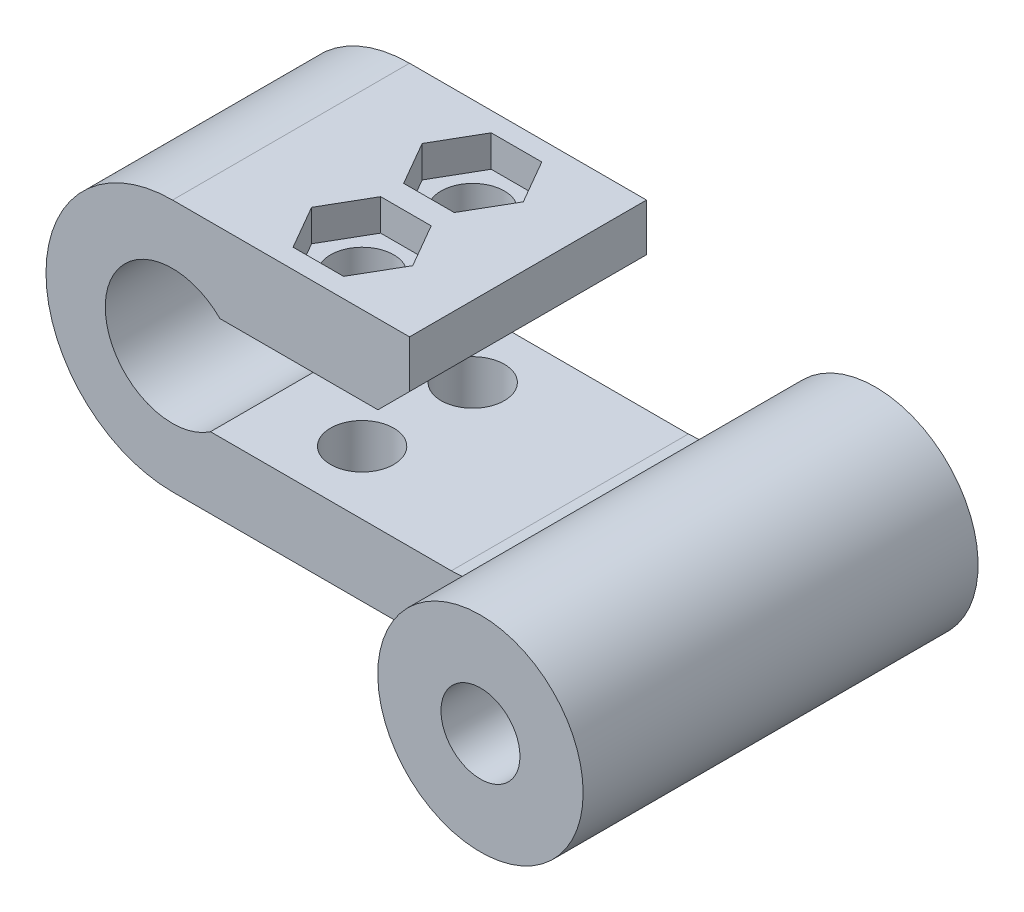
SolidWorks part; units mm, degrees
ref_plane "Front Plane" through (0, 0, 0) normal (0, 0, 1) x (1, 0, 0)
ref_plane "Top Plane" through (0, 0, 0) normal (0, 1, 0) x (1, 0, 0)
ref_plane "Right Plane" through (0, 0, 0) normal (1, 0, 0) x (0, 0, -1)
sketch "Sketch1" plane through (0, 0, 0) normal (0, 0, 1) x (1, 0, 0)
  line L0 (-1.8201, 14.7543) -> (13.1799, 14.7543)
  line L1 (13.1799, 14.7543) -> (13.1799, 11.7543)
  line L2 (13.1799, 11.7543) -> (11.1799, 9.7543)
  line L3 (11.1799, 9.7543) -> (1.1799, 9.7543)
  line L4 (-1.8305, -1.2457) -> (27.6695, -1.2457)
  line L6 (21.4848, 3.2543) -> (0.5804, 3.2543)
  arc A0 (-1.8201, 14.7543) -> (-1.8305, -1.2457) centre (-1.8305, 6.7543) ccw
  arc A1 (1.1799, 9.7543) -> (0.5804, 3.2543) centre (-1.8305, 6.7543) ccw
  arc A2 (27.6695, -1.2457) -> (21.4848, 3.2543) centre (27.6695, 5.2543) ccw
  circle A3 centre (27.6695, 5.2543) radius 2.5
  dimension "D4" = 6.5
  dimension "D5" = 8
  dimension "D7" = 15
  dimension "D9" = 4.25
  dimension "D3" = 13
  dimension "D13" = 5
  dimension "D1" = 3
  dimension "D2" = 10
  dimension "D6" = 29.5
  dimension "D8" = 5
  dimension "D10" = 135
  dimension "D11" = 0.5804
  dimension "D12" = 3.2543
extrude "Boss-Extrude1" add sketch "Sketch1" along normal blind 15 contours A2 L6 A1 L3 L2 L1 L0 A0 L4 region at (5.6799, 14.2861, 0)
extrude "Boss-Extrude2" add sketch "Sketch1<3>" along normal blind 25 contours A2 A3 region at (5.6799, 14.2861, 0)
sketch "Sketch1<3>" plane through (0, 0, 0) normal (0, 0, 1) x (1, 0, 0) same geometry as "Sketch1"
fillet "Fillet1" radius 6 1 edges at (21.4848, 3.2543, 12.5)
sketch "Sketch4" plane through (0, 0, 25) normal (0, 0, 1) x (1, 0, 0)
  line L0 (13.1799, 14.7543) -> (13.1799, 11.7543)
  line L1 (13.1799, 11.7543) -> (11.1799, 9.7543)
  line L2 (11.1799, 9.7543) -> (1.1799, 9.7543)
  line L3 (13.1799, 14.7543) -> (-1.8201, 14.7543)
  line L4 (0.5804, 3.2543) -> (15.8267, 3.2543)
  line L5 (-1.8305, -1.2457) -> (27.6695, -1.2457)
  arc A0 (-1.8201, 14.7543) -> (-1.8305, -1.2457) centre (-1.8305, 6.7543) ccw
  arc A1 (1.1799, 9.7543) -> (0.5804, 3.2543) centre (-1.8305, 6.7543) ccw
  circle A2 centre (27.6695, 5.2543) radius 6.5
  line M2 (-1.8305, -1.2457) -> (27.6695, -1.2457)
  arc M4 (21.5112, 7.3343) -> (15.8267, 3.2543) centre (15.8267, 9.2543) cw
  line M5 (15.8267, 3.2543) -> (0.5804, 3.2543)
  arc M6 (0.5804, 3.2543) -> (1.1799, 9.7543) centre (-1.8305, 6.7543) cw
  line M7 (1.1799, 9.7543) -> (11.1799, 9.7543)
  line M8 (11.1799, 9.7543) -> (13.1799, 11.7543)
  line M9 (13.1799, 11.7543) -> (13.1799, 14.7543)
  line M10 (13.1799, 14.7543) -> (-1.8201, 14.7543)
  arc M11 (-1.8201, 14.7543) -> (-1.8305, -1.2457) centre (-1.8305, 6.7543) ccw
extrude "Cut-Extrude1" cut sketch "Sketch4" against normal blind 10 contours A2 M4 M5 M6 M7 M8 M9 M10 M11 M2 region at (12.7722, 13.2543, 25)
fillet "Fillet2" radius 3 1 edges at (22.3888, 1.4641, 15)
sketch "Sketch5" plane through (0, 14.7543, 0) normal (0, 1, 0) x (1, 0, 0)
  line L0 (-1.8201, 0) -> (13.1799, 0) construction
  line L1 (13.1799, -15) -> (13.1799, 0) construction
  circle A0 centre (6.1799, -4) radius 2
  circle A1 centre (6.1799, -11) radius 2
  dimension "D1" = 4
  dimension "D2" = 4
  dimension "D4" = 4
  dimension "D3" = 7
  dimension "D5" = 7
  dimension "D6" = 7
extrude "Cut-Extrude2" cut sketch "Sketch5" against normal through all
sketch "Sketch6" plane through (0, 14.7543, 0) normal (0, 1, 0) x (1, 0, 0)
  line L0 (-1.8201, -15) -> (-1.8201, 0) construction
  line L1 (9.3799, -4) -> (7.7799, -1.2287)
  line L2 (7.7799, -1.2287) -> (4.5799, -1.2287)
  line L3 (4.5799, -1.2287) -> (2.9799, -4)
  line L4 (2.9799, -4) -> (4.5799, -6.7713)
  line L5 (4.5799, -6.7713) -> (7.7799, -6.7713)
  line L6 (7.7799, -6.7713) -> (9.3799, -4)
  line L7 (9.3799, -11) -> (7.7799, -8.2287)
  line L8 (7.7799, -8.2287) -> (4.5799, -8.2287)
  line L9 (4.5799, -8.2287) -> (2.9799, -11)
  line L10 (2.9799, -11) -> (4.5799, -13.7713)
  line L11 (4.5799, -13.7713) -> (7.7799, -13.7713)
  line L12 (7.7799, -13.7713) -> (9.3799, -11)
  circle A0 centre (6.1799, -4) radius 2.7713 construction
  circle A1 centre (6.1799, -11) radius 2.7713 construction
  dimension "D1" = 3.2
  dimension "D2" = 9.6
extrude "Cut-Extrude3" cut sketch "Sketch6" against normal blind 2
